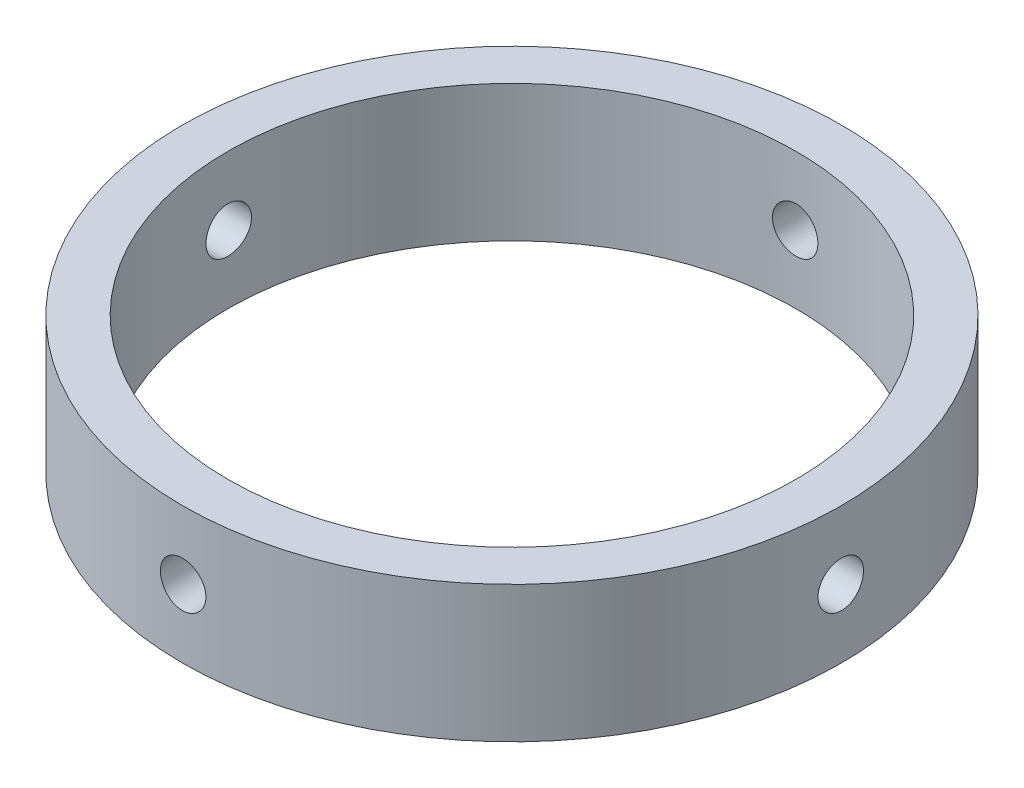
SolidWorks part; units mm, degrees
ref_plane "Front Plane" through (0, 0, 0) normal (0, 0, 1) x (1, 0, 0)
ref_plane "Top Plane" through (0, 0, 0) normal (0, 1, 0) x (1, 0, 0)
ref_plane "Right Plane" through (0, 0, 0) normal (1, 0, 0) x (0, 0, -1)
sketch "Sketch1" plane through (0, 0, 0) normal (0, 1, 0) x (1, 0, 0)
  circle A0 centre (0, 0) radius 39.6875
  circle A1 centre (0, 0) radius 46.0375
  dimension "D1" = 79.375
  dimension "D2" = 6.35
extrude "Boss-Extrude1" add sketch "Sketch1" along normal blind 19.05
sketch "Sketch7" plane through (0, 0, 0) normal (0, 0, 1) x (1, 0, 0)
  circle A0 centre (0, 9.525) radius 3.175
  point P3 (0, 0)
  dimension "D1" = 6.35
  dimension "D2" = 9.525
sketch "Sketch10" plane through (0, 0, 0) normal (1, 0, 0) x (0, 0, -1)
  circle A0 centre (0, 9.525) radius 3.175
  point P3 (0, 0)
  dimension "D1" = 6.35
extrude "Cut-Extrude4" cut sketch "Sketch7" against normal blind 76.2 and the other way blind 76.2
extrude "Cut-Extrude5" cut sketch "Sketch10" against normal blind 76.2 and the other way blind 76.2
